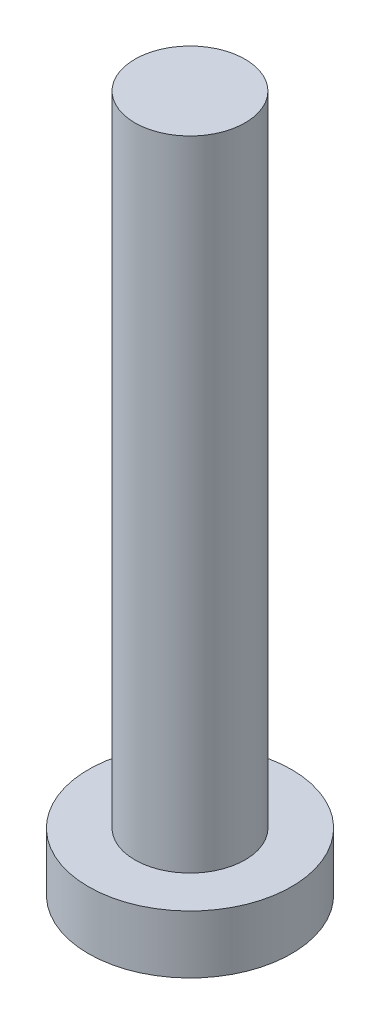
SolidWorks part; units mm, degrees
ref_plane "Front Plane" through (0, 0, 0) normal (0, 0, 1) x (1, 0, 0)
ref_plane "Top Plane" through (0, 0, 0) normal (0, 1, 0) x (1, 0, 0)
ref_plane "Right Plane" through (0, 0, 0) normal (1, 0, 0) x (0, 0, -1)
sketch "Sketch1" plane through (0, 0, 0) normal (0, 1, 0) x (1, 0, 0)
  circle A0 centre (0, 0) radius 0.95
  circle A1 centre (0, 0) radius 1.75
  dimension "D1" = 3.5
  dimension "D2" = 1.9
extrude "Boss-Extrude1" add sketch "Sketch1" against normal blind 1 contours A1
extrude "Boss-Extrude2" add sketch "Sketch1<4>" along normal blind 11 contours A0
sketch "Sketch1<4>" plane through (0, 0, 0) normal (0, 1, 0) x (1, 0, 0) same geometry as "Sketch1"
